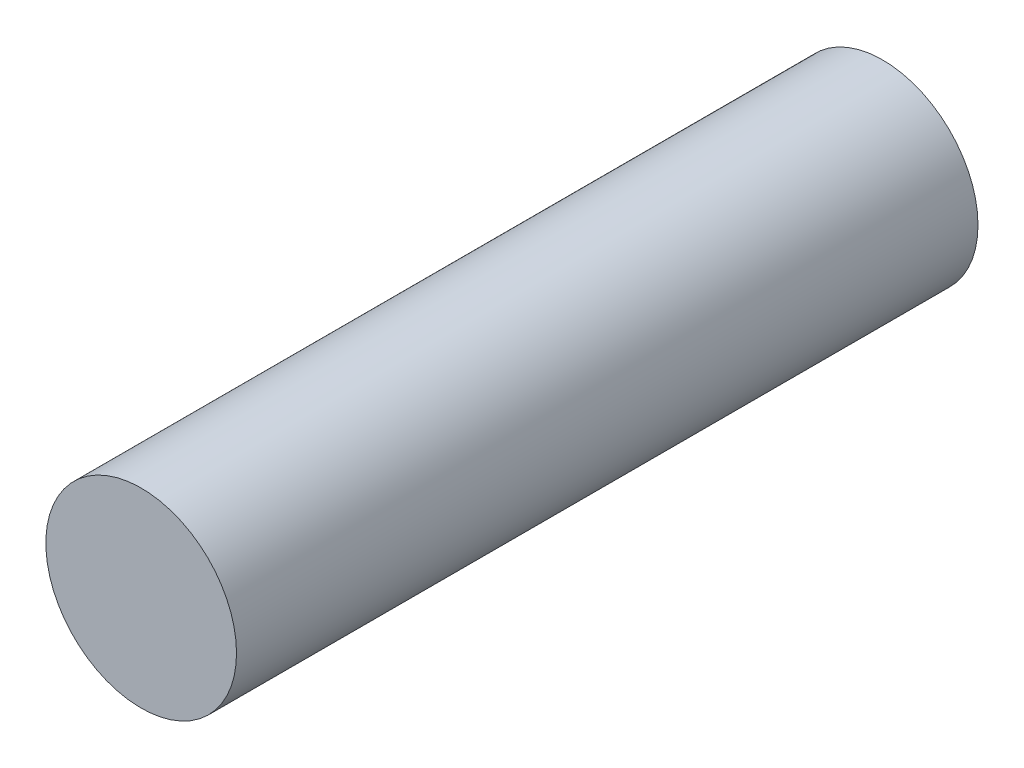
SolidWorks part; units mm, degrees
material "AISI 316 Annealed Stainless Steel Bar (SS)"
ref_plane "Front Plane" through (0, 0, 0) normal (0, 0, 1) x (1, 0, 0)
ref_plane "Top Plane" through (0, 0, 0) normal (0, 1, 0) x (1, 0, 0)
ref_plane "Right Plane" through (0, 0, 0) normal (1, 0, 0) x (0, 0, -1)
sketch "Sketch1" plane through (0, 0, 0) normal (0, 0, 1) x (1, 0, 0)
  circle A2 centre (0, 0) radius 9
  dimension "D1" = 18
extrude "Boss-Extrude1" add sketch "Sketch1" along normal blind 70 contours A2 region at (0, 0, 0)
